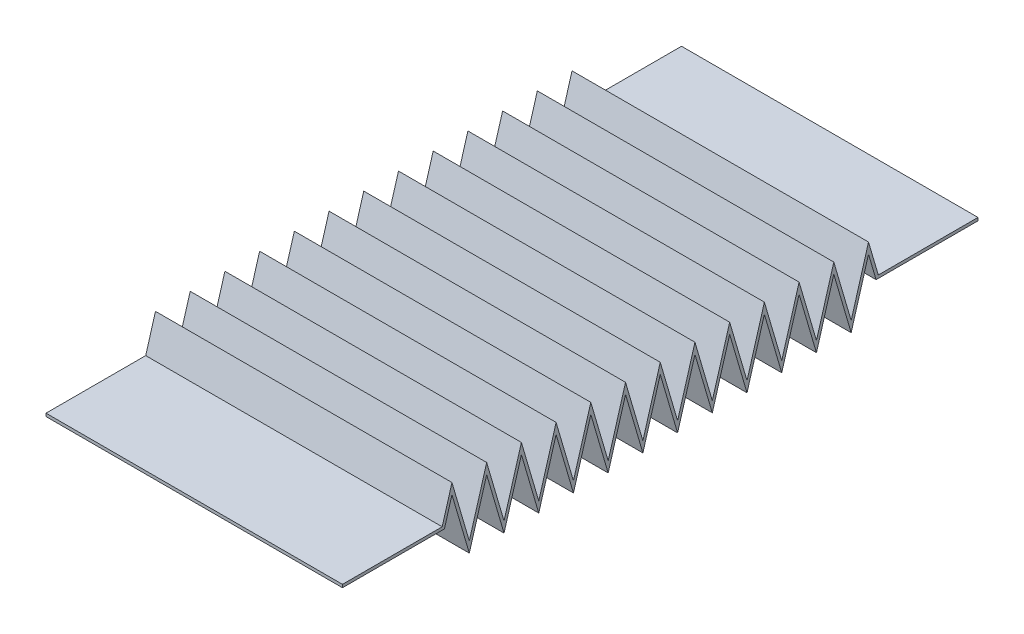
SolidWorks part; units mm, degrees
ref_plane "Front Plane" through (0, 0, 0) normal (0, 0, 1) x (1, 0, 0)
ref_plane "Top Plane" through (0, 0, 0) normal (0, 1, 0) x (1, 0, 0)
ref_plane "Right Plane" through (0, 0, 0) normal (1, 0, 0) x (0, 0, -1)
sketch "Sketch2" plane through (0, 0, 0) normal (0, 0, 1) x (1, 0, 0)
  line L1 (-27.5, 10) -> (27.5, 10)
  line L2 (-27.5, 10) -> (-27.5, 0)
  line L3 (-27.5, 0) -> (27.5, 0)
  line L4 (27.5, 10) -> (27.5, 0)
  point P4 (0, 0)
  dimension "D1" = 10
  dimension "D2" = 55
sketch "Sketch3" plane through (0, 0, 0) normal (1, 0, 0) x (0, 0, -1)
  line L0 (0, 10) -> (107.1774, 10) construction
  line L1 (0, 0) -> (107.1774, 0) construction
  line L2 (107.1774, 5.25) -> (107.1774, -12.75) construction
  line L3 (17, 5) -> (18.4635, 10)
  line L4 (18.4635, 10) -> (21.3906, 0)
  line L5 (21.3906, 0) -> (24.3177, 10)
  line L6 (24.3177, 10) -> (27.2448, 0)
  line L7 (27.2448, 0) -> (30.1719, 10)
  line L8 (30.1719, 10) -> (33.099, 0)
  line L9 (33.099, 0) -> (36.0261, 10)
  line L10 (36.0261, 10) -> (38.9532, 0)
  line L11 (38.9532, 0) -> (41.8803, 10)
  line L12 (41.8803, 10) -> (44.8074, 0)
  line L13 (44.8074, 0) -> (47.7345, 10)
  line L14 (47.7345, 10) -> (50.6616, 0)
  line L15 (50.6616, 0) -> (53.5887, 10)
  line L16 (53.5887, 10) -> (56.5158, 0)
  line L17 (56.5158, 0) -> (59.4429, 10)
  line L18 (59.4429, 10) -> (62.37, 0)
  line L19 (0, 10) -> (0, 0) construction
  line L20 (62.37, 0) -> (65.2971, 10)
  line L21 (65.2971, 10) -> (68.2242, 0)
  line L22 (68.2242, 0) -> (71.1513, 10)
  line L23 (71.1513, 10) -> (74.0784, 0)
  line L24 (74.0784, 0) -> (77.0055, 10)
  line L25 (77.0055, 10) -> (79.9326, 0)
  line L26 (79.9326, 0) -> (82.8597, 10)
  line L27 (82.8597, 10) -> (85.7867, 0)
  line L28 (85.7867, 0) -> (88.7138, 10)
  line L29 (88.7138, 10) -> (90.1774, 5)
  line L30 (107.1774, 10) -> (107.1774, 0) construction
  line L31 (17, 5) -> (0, 5)
  line L32 (90.1774, 5) -> (107.1774, 5)
  dimension "D2" = 17
  dimension "D1" = 10
  dimension "D3" = 17
extrude "Extrude-Thin1" add sketch "Sketch3" against normal mid plane 50 thin thin type mid plane wall 0.5
